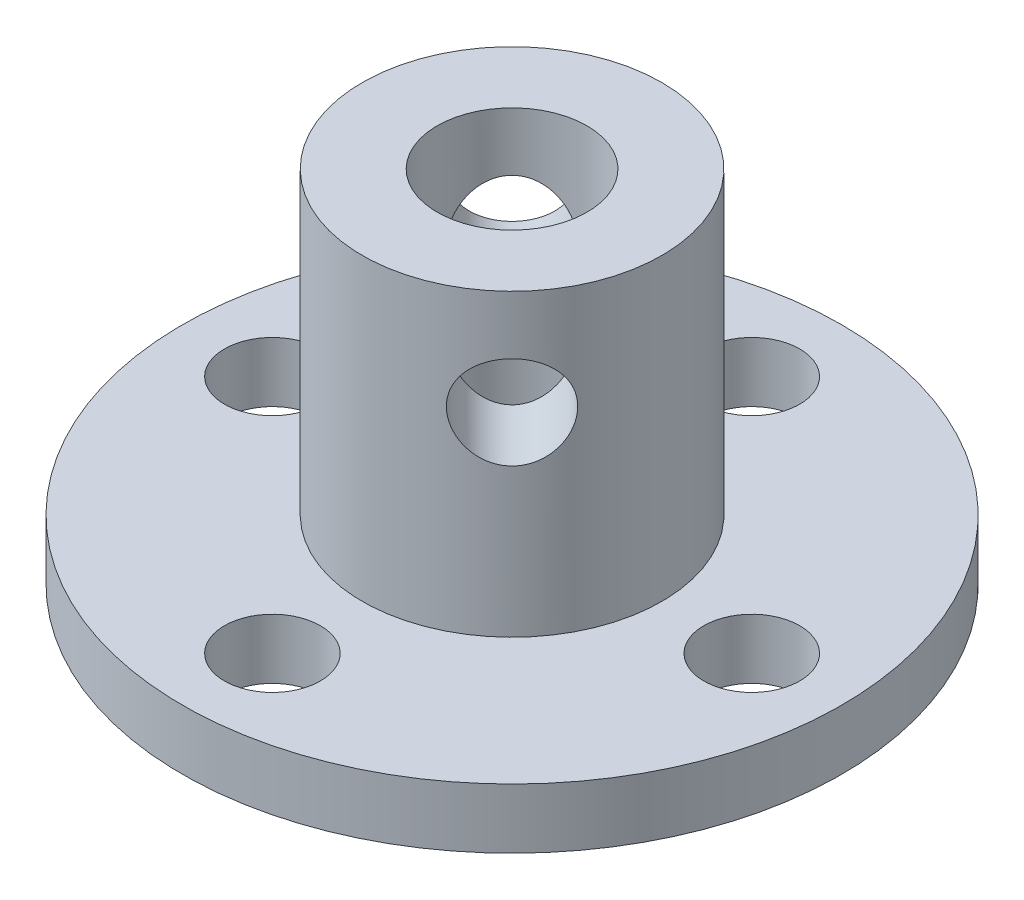
SolidWorks part; units mm, degrees
ref_plane "前视基准面" through (0, 0, 0) normal (0, 0, 1) x (1, 0, 0)
ref_plane "上视基准面" through (0, 0, 0) normal (0, 1, 0) x (1, 0, 0)
ref_plane "右视基准面" through (0, 0, 0) normal (1, 0, 0) x (0, 0, -1)
sketch "草图1" plane through (0, 0, 0) normal (0, 0, 1) x (1, 0, 0)
  line L0 (-2.5, 0.014) -> (-11, 0.014)
  line L1 (-11, 0.014) -> (-11, 2.014)
  line L2 (-11, 2.014) -> (-5, 2.014)
  line L3 (-5, 2.014) -> (-5, 12.014)
  line L4 (-5, 12.014) -> (-2.5, 12.014)
  line L5 (-2.5, 12.014) -> (-2.5, 0.014)
  line L6 (0, 0) -> (0, 12.028) construction
  dimension "D1" = 5
  dimension "D2" = 10
  dimension "D3" = 2
  dimension "D4" = 10
  dimension "D5" = 22
revolve "旋转1" add sketch "草图1" angle 360 about L6
sketch "草图2" plane through (0, 0.014, 0) normal (0, -1, 0) x (1, 0, 0)
  circle A0 centre (-8, 0) radius 1.6
  circle A1 centre (0, 0) radius 2.5 construction
  circle A2 centre (0, 8) radius 1.6
  circle A3 centre (8, 0) radius 1.6
  circle A4 centre (0, -8) radius 1.6
  point P4 (0, 0)
  point P15 (0, 0)
  dimension "D1" = 3.2
  dimension "D2" = 8
  dimension "D3" = 4
extrude "切除-拉伸1" cut sketch "草图2" against normal blind 10
ref_axis "基准轴1" through (0, 12.014, 0) along (0, -1, 0)
ref_plane "基准面1" through (0, 0, 0) normal (0.7071, 0, 0.7071) x (0, -1, 0)
sketch "草图3" plane through (0, 0, 0) normal (0.7071, 0, 0.7071) x (0, -1, 0)
  line L0 (-12.014, 0) -> (-0.014, 0) construction
  line L1 (-2.014, 11) -> (-2.014, -11) construction
  circle A0 centre (-8.514, 0) radius 1.55
  dimension "D1" = 6.5
  dimension "D2" = 3.1
extrude "切除-拉伸2" cut sketch "草图3" against normal blind 10 and the other way blind 10
